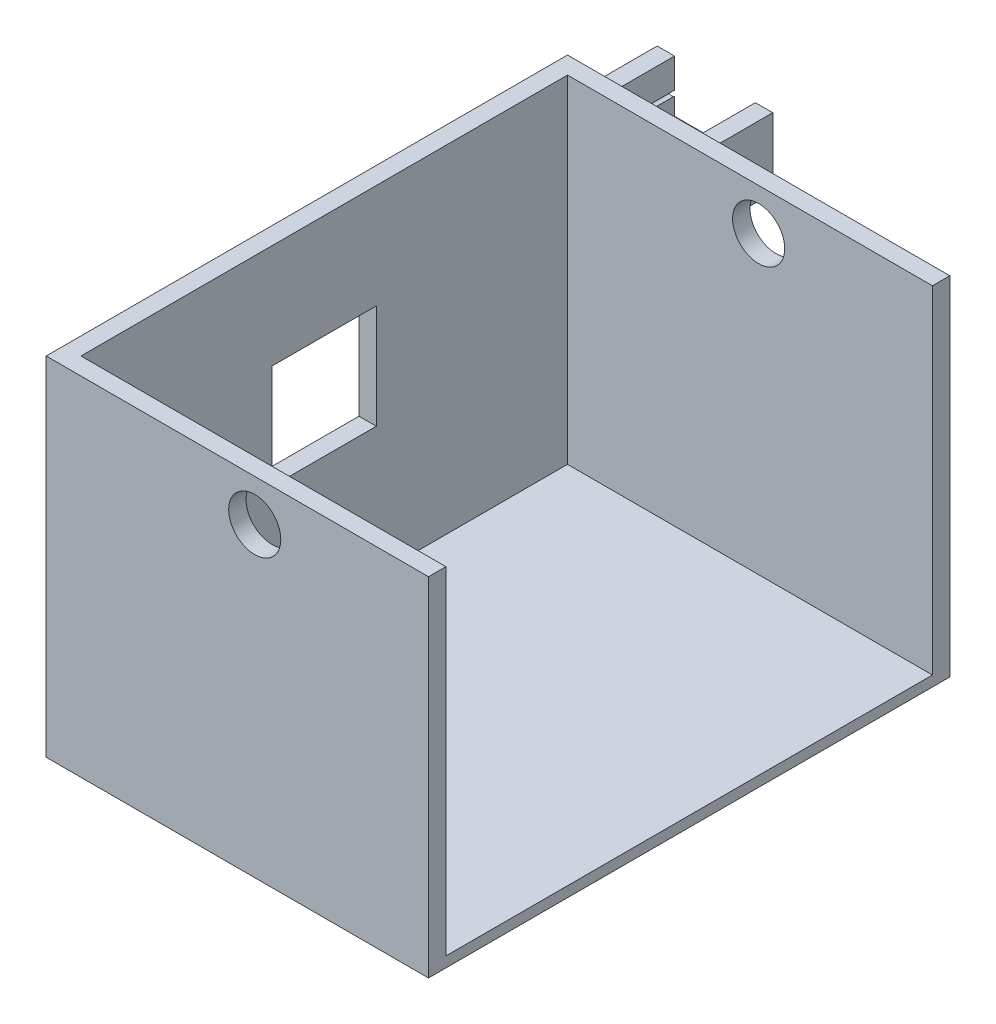
SolidWorks part; units mm, degrees
ref_plane "Front Plane" through (0, 0, 0) normal (0, 0, 1) x (1, 0, 0)
ref_plane "Top Plane" through (0, 0, 0) normal (0, 1, 0) x (1, 0, 0)
ref_plane "Right Plane" through (0, 0, 0) normal (1, 0, 0) x (0, 0, -1)
sketch "CollectorSize" plane through (0, 0, 0) normal (0, 1, 0) x (1, 0, 0)
  line L1 (33.1119, 70.6082) -> (143.1119, 70.6082)
  line L2 (33.1119, 70.6082) -> (33.1119, -79.3918)
  line L3 (33.1119, -79.3918) -> (143.1119, -79.3918)
  line L4 (143.1119, 70.6082) -> (143.1119, -79.3918)
  dimension "D1" = 110
  dimension "D2" = 150
extrude "Boss-Extrude1" add sketch "CollectorSize" along normal blind 200
sketch "CollectorShape" plane through (0, 0, 79.3918) normal (0, 0, 1) x (1, 0, 0)
  line L1 (143.1119, 100) -> (33.1119, 100)
  line L2 (33.1119, 200) -> (33.1119, 0) construction
  line L5 (33.1119, 100) -> (33.1119, 200)
  line L6 (33.1119, 200) -> (143.1119, 200)
  line L7 (143.1119, 200) -> (143.1119, 100)
  line L8 (143.1119, 200) -> (143.1119, 0) construction
extrude "Cut-Extrude1" cut sketch "CollectorShape" against normal through all
sketch "CollectorWalls" plane through (0, 100, 0) normal (0, 1, 0) x (1, 0, 0)
  line L1 (38.1119, 65.6082) -> (167.757, 65.6082)
  line L2 (38.1119, 65.6082) -> (38.1119, -74.3918)
  line L3 (38.1119, -74.3918) -> (167.757, -74.3918)
  line L4 (167.757, 65.6082) -> (167.757, -74.3918)
  line L5 (33.1119, 70.6082) -> (143.1119, 70.6082) construction
  line L6 (33.1119, -79.3918) -> (143.1119, -79.3918) construction
  line L7 (33.1119, 70.6082) -> (33.1119, -79.3918) construction
  dimension "D2" = 5
  dimension "5" = 5
  dimension "D3" = 5
extrude "Cut-Extrude2" cut sketch "CollectorWalls" against normal offset from surface (97 mm away) 3 up to face at (88.1119, 0, 4.3918)
sketch "Sketch1" plane through (0, 0, 79.3918) normal (0, 0, 1) x (1, 0, 0)
  line L0 (33.1119, 100) -> (143.1119, 100) construction
  line L2 (143.1119, 100) -> (143.1119, 0) construction
  circle A0 centre (93.1119, 88) radius 7.5
  dimension "D1" = 12
  dimension "D2" = 15
  dimension "D3" = 50
extrude "Cut-Extrude5" cut sketch "Sketch1" against normal through all both and the other way through all
sketch "Sketch2" plane through (33.1119, 0, 0) normal (-1, 0, 0) x (0, 0, 1)
  line L0 (-70.6082, 100) -> (79.3918, 100) construction
  line L1 (-10.6082, 70) -> (19.3918, 70)
  line L2 (-10.6082, 70) -> (-10.6082, 40)
  line L3 (-10.6082, 40) -> (19.3918, 40)
  line L4 (19.3918, 70) -> (19.3918, 40)
  line L7 (-70.6082, 100) -> (-70.6082, 0) construction
  dimension "D1" = 60
  dimension "D2" = 30
  dimension "D3" = 30
  dimension "D4" = 30
extrude "Boss-Extrude2" [suppressed] add sketch "Sketch2" along normal blind 242
sketch "Sketch3" plane through (0, 0, -70.6082) normal (0, 0, -1) x (-1, 0, 0)
  line L0 (-46.3699, 81.9) -> (-68.2199, 81.9) construction
  line L1 (-45.6699, 81.9) -> (-68.9199, 81.9)
  line L7 (-45.6699, 96.9) -> (-40.6699, 96.9)
  line L8 (-40.6699, 76.9) -> (-40.6699, 96.9)
  line L11 (-68.9199, 96.9) -> (-73.9199, 96.9)
  line L12 (-73.9199, 76.9) -> (-73.9199, 96.9)
  line L13 (-68.9199, 96.9) -> (-68.9199, 81.9)
  line L14 (-45.6699, 81.9) -> (-45.6699, 96.9)
  line L15 (-73.9199, 76.9) -> (-40.6699, 76.9)
  line L16 (-68.5199, 82.2) -> (-68.5199, 93.8) construction
  line L17 (-46.0699, 93.8) -> (-46.0699, 82.2) construction
  point P1 (-46.0699, 92.9295)
  point P10 (-57.2949, 81.9)
  point P18 (-68.5199, 86.1279)
  dimension "D1" = 5
  dimension "D2" = 5
  dimension "D3" = 20
  dimension "D4" = 33.25
  dimension "D5" = 0.4
extrude "Boss-Extrude3" add sketch "Sketch3" along normal blind 18.25
sketch "Sketch4" plane through (0, 0, -88.8582) normal (0, 0, -1) x (-1, 0, 0)
  line L1 (-70.9949, 89) -> (-70.9949, 87) construction
  circle A0 centre (-44.876, 87.6506) radius 1.0831
  arc A1 (-71.7328, 87.325) -> (-71.7328, 88.675) centre (-70.9949, 88) ccw construction
  circle A3 centre (-70.9949, 88) radius 1
  point P2 (-70.9949, 88)
extrude "Cut-Extrude6" cut sketch "Sketch4" against normal blind 18.25
sketch "Sketch5" [suppressed] plane through (0, 0, -10.6082) normal (0, 0, -1) x (-1, 0, 0)
  line L0 (178.8881, 70) -> (178.8881, 40) construction
  line L1 (208.8881, 70) -> (-33.1119, 70) construction
  line L2 (208.8881, 40) -> (-33.1119, 40) construction
  line L3 (208.8881, 70) -> (208.8881, 40) construction
  circle A0 centre (178.8881, 55) radius 15
  point P3 (178.8881, 55)
  dimension "D1" = 30
  dimension "D2" = 30
extrude "Boss-Extrude4" [suppressed] add sketch "Sketch5" along normal blind 10
extrude "Cut-Extrude7" cut sketch "Sketch2<2>" against normal blind 10
sketch "Sketch2<2>" plane through (33.1119, 0, 0) normal (-1, 0, 0) x (0, 0, 1) same geometry as "Sketch2"
